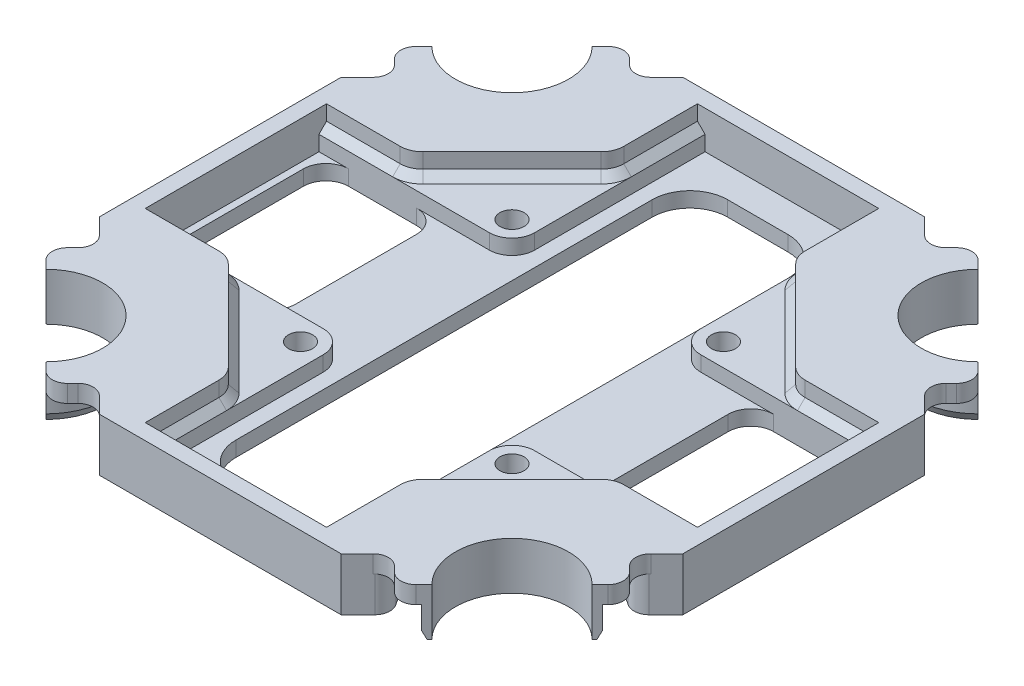
SolidWorks part; units mm, degrees
ref_plane "Front Plane" through (0, 0, 0) normal (0, 0, 1) x (1, 0, 0)
ref_plane "Top Plane" through (0, 0, 0) normal (0, 1, 0) x (1, 0, 0)
ref_plane "Right Plane" through (0, 0, 0) normal (1, 0, 0) x (0, 0, -1)
sketch "Sketch1" plane through (0, 0, 0) normal (0, 1, 0) x (1, 0, 0)
  line L1 (38.6274, 16) -> (16, 38.6274)
  line L2 (16, 38.6274) -> (-16, 38.6274)
  line L3 (-16, 38.6274) -> (-38.6274, 16)
  line L4 (-38.6274, 16) -> (-38.6274, -16)
  line L5 (-38.6274, -16) -> (-16, -38.6274)
  line L6 (-16, -38.6274) -> (16, -38.6274)
  line L7 (16, -38.6274) -> (38.6274, -16)
  line L8 (38.6274, -16) -> (38.6274, 16)
  circle A0 centre (0, 0) radius 38.6274 construction
  dimension "D1" = 32
extrude "Boss-Extrude1" add sketch "Sketch1" along normal blind 7
sketch "Sketch2" plane through (0, 7, 0) normal (0, 1, 0) x (1, 0, 0)
  line L0 (0, 0) -> (23.0693, 23.0694)
  line L2 (38.6257, 23.0694) -> (30.8474, 15.2911)
  line L4 (23.0694, 38.6257) -> (15.2913, 30.8476)
  line L5 (15.2913, 30.8476) -> (30.8474, 15.2911)
  line L6 (30.8476, -15.2913) -> (15.2911, -30.8474)
  line L7 (38.6257, -23.0694) -> (30.8476, -15.2913)
  line L8 (23.0694, -38.6257) -> (15.2911, -30.8474)
  line L9 (-15.2913, -30.8476) -> (-30.8474, -15.2911)
  line L10 (-23.0694, -38.6257) -> (-15.2913, -30.8476)
  line L11 (-38.6257, -23.0694) -> (-30.8474, -15.2911)
  line L12 (-30.8476, 15.2913) -> (-15.2911, 30.8474)
  line L13 (-38.6257, 23.0694) -> (-30.8476, 15.2913)
  line L14 (-23.0694, 38.6257) -> (-15.2911, 30.8474)
  line L15 (23.0694, -38.6257) -> (38.6257, -23.0694)
  line L16 (-38.6257, -23.0694) -> (-23.0694, -38.6257)
  line L17 (-38.6257, 23.0694) -> (-23.0694, 38.6257)
  line L18 (23.0694, 38.6257) -> (38.6257, 23.0694)
  point P26 (0, 0)
  line M6 (38.6274, 16) -> (16, 38.6274)
  line M8 (-16, 38.6274) -> (-38.6274, 16)
  line M10 (-38.6274, -16) -> (-16, -38.6274)
  line M12 (16, -38.6274) -> (38.6274, -16)
  dimension "D1" = 4
extrude "Boss-Extrude2" add sketch "Sketch2" against normal blind 2.3 contours L14 L17 L13 M8 | L2 L18 L4 M6 | L8 L15 L7 M12 | L11 L16 L10 M10 region at (29.0806, 7, -29.0806) region at (29.0806, 7, 29.0806) region at (-29.0806, 7, 29.0806) region at (-29.0806, 7, -29.0806)
sketch "Sketch3" plane through (0, 4.7, 0) normal (0, -1, 0) x (1, 0, 0)
  line L0 (-35.0919, 19.5355) -> (-19.5355, 35.0919)
  line L1 (19.5355, 35.0919) -> (35.0919, 19.5355)
  line L2 (35.0919, -19.5355) -> (19.5355, -35.0919)
  line L3 (-19.5355, -35.0919) -> (-35.0919, -19.5355)
  circle A0 centre (-27.3137, 27.3137) radius 11
  circle A1 centre (27.3137, 27.3137) radius 11
  circle A2 centre (27.3137, -27.3137) radius 11
  circle A3 centre (-27.3137, -27.3137) radius 11
  point P21 (0, 0)
  line M3 (-35.0919, 19.5355) -> (-19.5355, 35.0919)
  dimension "D1" = 4
extrude "Cut-Extrude1" cut sketch "Sketch3" along normal blind 10 contours A0 M3 | L1 A1 | L2 A2 | L3 A3 region at (-24.0125, 4.7, 24.0125) region at (24.0125, 4.7, 24.0125) region at (24.0125, 4.7, -24.0125) region at (-24.0125, 4.7, -24.0125)
sketch "Sketch4" plane through (0, 4.7, 0) normal (0, -1, 0) x (-1, 0, 0)
  line L0 (38.6257, -23.0694) -> (23.0694, -38.6257) construction
  line L1 (24.8725, -36.8226) -> (25.5442, -36.1508)
  line L2 (36.1508, -25.5442) -> (36.8226, -24.8725)
  line L3 (-36.8226, -24.8725) -> (-36.1508, -25.5442)
  line L4 (-25.5442, -36.1508) -> (-24.8725, -36.8226)
  line L5 (-24.8725, 36.8226) -> (-25.5442, 36.1508)
  line L6 (-36.1508, 25.5442) -> (-36.8226, 24.8725)
  line L7 (36.8226, 24.8725) -> (36.1508, 25.5442)
  line L8 (25.5442, 36.1508) -> (24.8725, 36.8226)
  arc A0 (36.8226, -24.8725) -> (24.8725, -36.8226) centre (30.8475, -30.8475) ccw
  arc A1 (36.1508, -25.5442) -> (25.5442, -36.1508) centre (30.8475, -30.8475) ccw
  arc A2 (-24.8725, -36.8226) -> (-36.8226, -24.8725) centre (-30.8475, -30.8475) ccw
  arc A3 (-25.5442, -36.1508) -> (-36.1508, -25.5442) centre (-30.8475, -30.8475) ccw
  arc A4 (-36.8226, 24.8725) -> (-24.8725, 36.8226) centre (-30.8475, 30.8475) ccw
  arc A5 (-36.1508, 25.5442) -> (-25.5442, 36.1508) centre (-30.8475, 30.8475) ccw
  arc A6 (24.8725, 36.8226) -> (36.8226, 24.8725) centre (30.8475, 30.8475) ccw
  arc A7 (25.5442, 36.1508) -> (36.1508, 25.5442) centre (30.8475, 30.8475) ccw
  point P28 (0, 0)
  dimension "D1" = 4
extrude "Boss-Extrude3" add sketch "Sketch4" along normal blind 4
sketch "Sketch5" plane through (0, 4.7, 0) normal (0, -1, 0) x (-1, 0, 0)
  line L0 (36.1508, -25.5442) -> (25.5442, -36.1508) construction
  circle A0 centre (30.8475, -30.8475) radius 7.5
  circle A1 centre (-30.8475, -30.8475) radius 7.5
  circle A2 centre (-30.8475, 30.8475) radius 7.5
  circle A3 centre (30.8475, 30.8475) radius 7.5
  point P13 (0, 0)
  dimension "D1" = 4
extrude "Cut-Extrude2" cut sketch "Sketch5" against normal blind 4
chamfer "Chamfer1" distance 1 distance2 0.5 4 edges at (24.8725, 0.7, 24.8725) (-24.8725, 0.7, 24.8725) (24.8725, 0.7, -24.8725) (-24.8725, 0.7, -24.8725) first distance on face at (27.86, 2.7, 27.86) first distance on face at (-27.86, 2.7, 27.86) first distance on face at (27.86, 2.7, -27.86) first distance on face at (-27.86, 2.7, -27.86)
fillet "Fillet1" radius 2 16 edges at (19.5355, 5.85, -35.0919) (23.0694, 5.85, -38.6257) (38.6257, 5.85, -23.0694) (35.0919, 5.85, -19.5355) (38.6257, 5.85, 23.0694) (35.0919, 5.85, 19.5355) (23.0694, 5.85, 38.6257) (19.5355, 5.85, 35.0919) (-19.5355, 5.85, 35.0919) (-23.0694, 5.85, 38.6257) (-38.6257, 5.85, 23.0694) (-35.0919, 5.85, 19.5355) (-35.0919, 5.85, -19.5355) (-38.6257, 5.85, -23.0694) (-19.5355, 5.85, -35.0919) (-23.0694, 5.85, -38.6257)
fillet "Fillet2" radius 2 8 edges at (-35.0919, 2.35, -19.5355) (-19.5355, 2.35, -35.0919) (-35.0919, 2.35, 19.5355) (-19.5355, 2.35, 35.0919) (35.0919, 2.35, 19.5355) (19.5355, 2.35, 35.0919) (19.5355, 2.35, -35.0919) (35.0919, 2.35, -19.5355)
sketch "Sketch6" plane through (0, 7, 0) normal (0, 1, 0) x (1, 0, 0)
  line L0 (-11, 26.5563) -> (-11, 36.5563)
  line L1 (26.5563, 11) -> (11, 26.5563)
  line L2 (11, 26.5563) -> (-11, 26.5563)
  line L3 (-11, 26.5563) -> (-26.5563, 11)
  line L4 (-26.5563, 11) -> (-26.5563, -11)
  line L5 (-26.5563, -11) -> (-11, -26.5563)
  line L6 (-11, -26.5563) -> (11, -26.5563)
  line L7 (11, -26.5563) -> (26.5563, -11)
  line L8 (26.5563, -11) -> (26.5563, 11)
  line L9 (11, 26.5563) -> (11, 36.5563)
  line L10 (11, 36.5563) -> (-11, 36.5563)
  line L11 (26.5563, -11) -> (36.5563, -11)
  line L12 (36.5563, -11) -> (36.5563, 11)
  line L13 (26.5563, 11) -> (36.5563, 11)
  line L14 (-11, -26.5563) -> (-11, -36.5563)
  line L15 (-11, -36.5563) -> (11, -36.5563)
  line L16 (11, -26.5563) -> (11, -36.5563)
  line L17 (-26.5563, 11) -> (-36.5563, 11)
  line L18 (-36.5563, 11) -> (-36.5563, -11)
  line L19 (-26.5563, -11) -> (-36.5563, -11)
  circle A0 centre (0, 0) radius 26.5563 construction
  point P28 (0, 0)
  dimension "D1" = 22
  dimension "D2" = 4
extrude "Cut-Extrude3" cut sketch "Sketch6" against normal blind 5 contours L7 L8 L1 L2 L3 L4 L5 L6 | L9 L10 L0 L2 | L19 L4 L17 L18 | L16 L6 L14 L15 | L13 L8 L11 L12 region at (0, 7, -31.5563) region at (0, 7, 0) region at (-31.5563, 7, 0) region at (31.5563, 7, 0) region at (0, 7, 31.5563)
sketch "Sketch7" plane through (0, 2, 0) normal (0, 1, 0) x (1, 0, 0)
  line L0 (0, 0) -> (0, 14)
  line L1 (0, 14) -> (-14, 14)
  circle A6 centre (-14, 14) radius 1.6
  circle A7 centre (14, 14) radius 1.6
  circle A8 centre (14, -14) radius 1.6
  circle A9 centre (-14, -14) radius 1.6
  point P13 (0, 0)
  point P17 (0, 0)
  dimension "D1" = 4
extrude "Cut-Extrude4" cut sketch "Sketch7" against normal blind 5 contours A9 | A9 | A6 | A6 | A6 | A7 | A7 | A8 | A8 region at (-15.5547, 2, -14) region at (14, 2, -14) region at (14, 2, 14) region at (-14, 2, 14)
sketch "Sketch8" plane through (0, 2, 0) normal (0, 1, 0) x (1, 0, 0)
  line L0 (35.6274, 2) -> (35.6274, -11)
  line L1 (26.5563, -11) -> (36.5563, -11) construction
  line L7 (0, -32.5563) -> (0, 32.5563) construction
  line L15 (0, 32.5563) -> (9, 32.5563)
  line L16 (9, 32.5563) -> (9, 20.5563)
  line L18 (0, 32.5563) -> (-9, 32.5563)
  line L19 (-9, 32.5563) -> (-9, 18.5563)
  line L27 (0, -32.5563) -> (-9, -32.5563)
  line L28 (-9, -32.5563) -> (-9, -22.5563)
  line L30 (0, -32.5563) -> (9, -32.5563)
  line L31 (9, -32.5563) -> (9, -20.5563)
  line L32 (-9, 18.5563) -> (-9, -22.5563)
  line L33 (9, 20.5563) -> (9, -20.5563)
  line L35 (35.6274, 2) -> (35.6274, 11)
  line L36 (35.6274, 11) -> (20.6274, 11)
  line L37 (-38.6274, 16) -> (-38.6274, -16) construction
  line L45 (35.6274, -11) -> (20.6274, -11)
  line L46 (20.6274, -11) -> (20.6274, 11)
  line L47 (-20.6274, -11) -> (-20.6274, 11)
  line L48 (-35.6274, -11) -> (-20.6274, -11)
  line L49 (-35.6274, 11) -> (-20.6274, 11)
  line L50 (-35.6274, 2) -> (-35.6274, 11)
  line L51 (-35.6274, 2) -> (-35.6274, -11)
  point P38 (0, 0)
  line M16 (26.5563, -11) -> (36.5563, -11)
  line M18 (36.5563, 11) -> (26.5563, 11)
  dimension "D1" = 3
  dimension "D2" = 15
extrude "Cut-Extrude5" cut sketch "Sketch8" against normal blind 22 contours L27 L7 L18 L19 L32 L28 | L7 L30 L31 L33 L16 L15 | L46 L45 L0 L35 L36 M16 M18 | L47 L49 L50 L51 L48 region at (28.1274, 2, 0) region at (-4.5, 2, 0) region at (4.5, 2, 0)
fillet "Fillet4" radius 5 4 edges at (-9, 1, 32.5563) (9, 1, 32.5563) (9, 1, -32.5563) (-9, 1, -32.5563)
fillet "Fillet5" radius 3 8 edges at (-35.6274, 1, 11) (20.6274, 1, 11) (35.6274, 1, 11) (20.6274, 1, -11) (35.6274, 1, -11) (-20.6274, 1, 11) (-20.6274, 1, -11) (-35.6274, 1, -11)
sketch "Sketch9" plane through (0, 2, 0) normal (0, 1, 0) x (1, 0, 0)
  line L0 (-28.2132, 11) -> (-14, 11)
  line L1 (-28.2132, 11) -> (-22.6888, 16.5244)
  line L2 (-11, 28.2132) -> (-11, 14)
  line L3 (-16.3881, 22.8251) -> (-11, 28.2132)
  line L4 (-22.6888, 16.5244) -> (-21.0649, 16.4915)
  line L5 (-11, 26.5563) -> (-26.5563, 11) construction
  line L6 (-16.3881, 22.8251) -> (-16.2063, 21.3501)
  line L7 (-11, 26.5563) -> (-26.5563, 11) construction
  line L8 (-16.2063, 21.3501) -> (-21.0649, 16.4915)
  line L30 (11, 28.2132) -> (11, 14)
  line L31 (11, 28.2132) -> (16.5244, 22.6888)
  line L32 (28.2132, 11) -> (14, 11)
  line L33 (22.8251, 16.3881) -> (28.2132, 11)
  line L34 (16.5244, 22.6888) -> (16.4915, 21.0649)
  line L35 (22.8251, 16.3881) -> (21.3501, 16.2063)
  line L36 (21.3501, 16.2063) -> (16.4915, 21.0649)
  line L37 (28.2132, -11) -> (14, -11)
  line L38 (28.2132, -11) -> (22.6888, -16.5244)
  line L39 (11, -28.2132) -> (11, -14)
  line L40 (16.3881, -22.8251) -> (11, -28.2132)
  line L41 (22.6888, -16.5244) -> (21.0649, -16.4915)
  line L42 (16.3881, -22.8251) -> (16.2063, -21.3501)
  line L43 (16.2063, -21.3501) -> (21.0649, -16.4915)
  line L44 (-11, -28.2132) -> (-11, -14)
  line L45 (-11, -28.2132) -> (-16.5244, -22.6888)
  line L46 (-28.2132, -11) -> (-14, -11)
  line L47 (-22.8251, -16.3881) -> (-28.2132, -11)
  line L48 (-16.5244, -22.6888) -> (-16.4915, -21.0649)
  line L49 (-22.8251, -16.3881) -> (-21.3501, -16.2063)
  line L50 (-21.3501, -16.2063) -> (-16.4915, -21.0649)
  arc A1 (-14, 11) -> (-11, 14) centre (-14, 14) ccw
  circle A2 centre (-14, 14) radius 1.6
  arc A10 (11, 14) -> (14, 11) centre (14, 14) ccw
  circle A11 centre (14, 14) radius 1.6
  arc A12 (14, -11) -> (11, -14) centre (14, -14) ccw
  circle A13 centre (14, -14) radius 1.6
  arc A14 (-11, -14) -> (-14, -11) centre (-14, -14) ccw
  circle A15 centre (-14, -14) radius 1.6
  point P49 (0.1363, -0.0701)
  point P51 (0, 0)
  dimension "D1" = 4
extrude "Boss-Extrude6" add sketch "Sketch9" along normal blind 2
sketch "Sketch12" plane through (0, 7, 0) normal (0, 1, 0) x (1, 0, 0)
  line L0 (-36.5563, 0) -> (-36.5563, 12)
  line L1 (-36.5563, 11) -> (-36.5563, -11) construction
  line L2 (-36.5563, 12) -> (-12, 12)
  line L4 (-12, -12) -> (-36.5563, -12)
  line L5 (-36.5563, 0) -> (-36.5563, -12)
  line L6 (0, 36.5563) -> (12, 36.5563)
  line L7 (12, 36.5563) -> (12, 12)
  line L9 (-12, 12) -> (-12, 36.5563)
  line L10 (0, 36.5563) -> (-12, 36.5563)
  line L11 (36.5563, 0) -> (36.5563, -12)
  line L12 (36.5563, -12) -> (12, -12)
  line L14 (12, 12) -> (36.5563, 12)
  line L15 (36.5563, 0) -> (36.5563, 12)
  line L16 (0, -36.5563) -> (-12, -36.5563)
  line L17 (-12, -36.5563) -> (-12, -12)
  line L19 (12, -12) -> (12, -36.5563)
  line L20 (0, -36.5563) -> (12, -36.5563)
  line L21 (-11, 14) -> (-11, 36.5563) construction
  line L22 (11, 36.5563) -> (-11, 36.5563) construction
  point P25 (0, 0)
  dimension "D1" = 12
  dimension "D2" = 24
  dimension "D4" = 1
  dimension "D5" = 0
  dimension "D3" = 4
extrude "Cut-Extrude6" cut sketch "Sketch12" against normal up to surface (3 mm away) up to face at (-14, 4, -12.4)
fillet "Fillet6" radius 3 8 edges at (-12, 5.5, 25.5563) (-25.5563, 5.5, 12) (12, 5.5, 25.5563) (25.5563, 5.5, 12) (12, 5.5, -25.5563) (25.5563, 5.5, -12) (-12, 5.5, -25.5563) (-25.5563, 5.5, -12)
chamfer "Chamfer3" distance 1 angle 45 20 edges at (-31.6777, 4, 12) (-12, 4, 31.6777) (12, 4, 31.6777) (31.6777, 4, 12) (12, 4, -31.6777) (12.2284, 4, -25.6509) (18.7782, 4, -18.7782) (25.6509, 4, -12.2284) (31.6777, 4, -12) (-12, 4, -31.6777) (-12.2284, 4, -25.6509) (-18.7782, 4, -18.7782) (-25.6509, 4, -12.2284) (-31.6777, 4, -12) (-25.6509, 4, 12.2284) (-18.7782, 4, 18.7782) (-12.2284, 4, 25.6509) (12.2284, 4, 25.6509) (18.7782, 4, 18.7782) (25.6509, 4, 12.2284)
